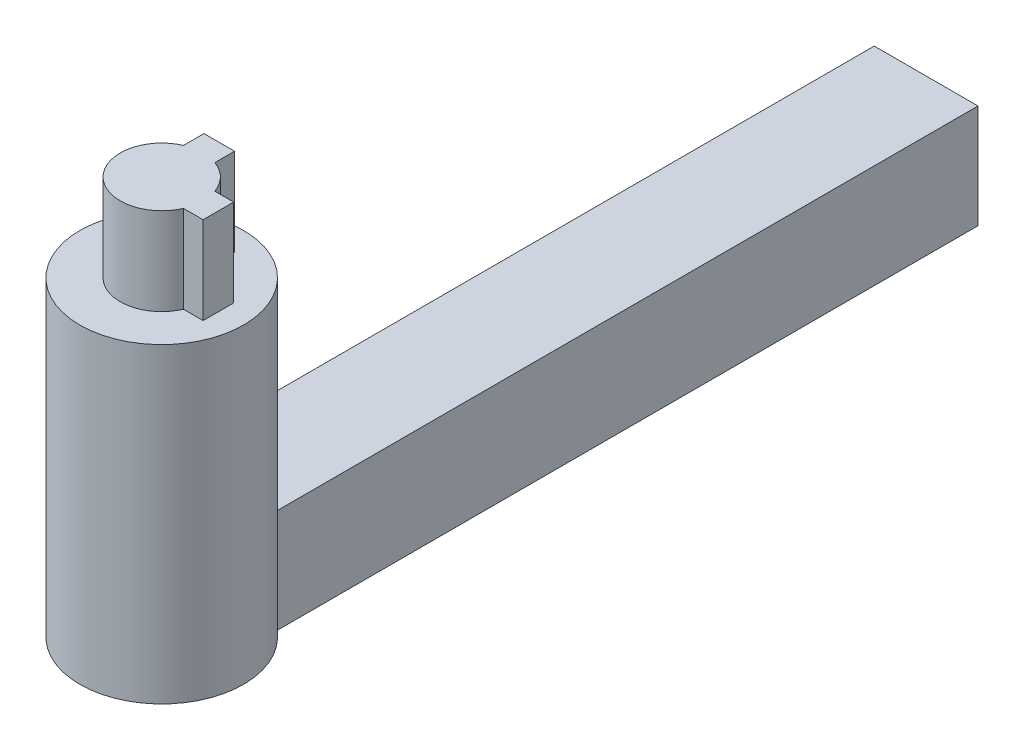
SolidWorks part; units mm, degrees
ref_plane "Front Plane" through (0, 0, 0) normal (0, 0, 1) x (1, 0, 0)
ref_plane "Top Plane" through (0, 0, 0) normal (0, 1, 0) x (1, 0, 0)
ref_plane "Right Plane" through (0, 0, 0) normal (1, 0, 0) x (0, 0, -1)
sketch "Sketch1" plane through (0, 0, 0) normal (0, 1, 0) x (1, 0, 0)
  line L1 (-4.75, 35) -> (4.75, 35)
  line L2 (-4.75, 35) -> (-4.75, -35)
  line L3 (-4.75, -35) -> (4.75, -35)
  line L4 (4.75, 35) -> (4.75, -35)
  line L5 (-4.75, 35) -> (4.75, -35) construction
  line L6 (-4.75, -35) -> (4.75, 35) construction
  point P0 (0, 0)
  dimension "D1" = 9.5
  dimension "D2" = 70
extrude "Boss-Extrude1" add sketch "Sketch1" along normal blind 9.5
sketch "Sketch2" plane through (0, 9.5, 0) normal (0, 1, 0) x (1, 0, 0)
  line L0 (-4.75, -35) -> (4.75, -35) construction
  circle A0 centre (0, -35) radius 7.5
  dimension "D1" = 15
extrude "Boss-Extrude2" add sketch "Sketch2" along normal blind 19 and the other way up to surface (9.5 mm away) other way up to face at (0, 0, 0)
sketch "Sketch3" plane through (0, 28.5, 0) normal (0, 1, 0) x (1, 0, 0)
  line L2 (-1.5, -31.5086) -> (-1.5, -29.6289)
  line L3 (-1.5, -29.6289) -> (1.2989, -29.6289)
  line L4 (1.2989, -31.4289) -> (1.2989, -29.6289)
  line L5 (3.5711, -33.7011) -> (5.2914, -33.7011)
  line L7 (3.4914, -36.5) -> (5.2914, -36.5)
  line L8 (5.2914, -33.7011) -> (5.2914, -36.5)
  arc A0 (-1.5, -31.5086) -> (3.4914, -36.5) centre (0, -35) ccw
  arc A1 (3.5711, -33.7011) -> (1.2989, -31.4289) centre (0, -35) ccw
  point P7 (3.246, -36.9757)
  dimension "D1" = 7.6
  dimension "D2" = 2.8
  dimension "D3" = 1.8
  dimension "D4" = 2.8
  dimension "D5" = 1.8
extrude "Boss-Extrude3" add sketch "Sketch3" along normal blind 8
